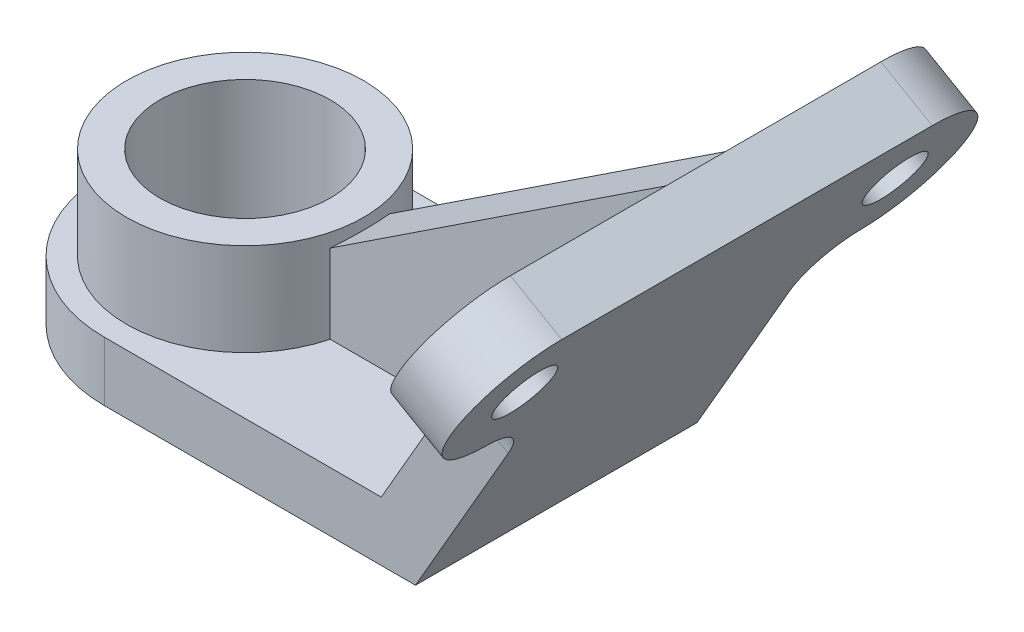
SolidWorks part; units mm, degrees
ref_plane "前视基准面" through (0, 0, 0) normal (0, 0, 1) x (1, 0, 0)
ref_plane "上视基准面" through (0, 0, 0) normal (0, 1, 0) x (1, 0, 0)
ref_plane "右视基准面" through (0, 0, 0) normal (1, 0, 0) x (0, 0, -1)
other "Configuration Table"
sketch "草图1" plane through (0, 0, 0) normal (0, 0, 1) x (1, 0, 0)
  line L1 (0, 0) -> (122, 0)
  line L2 (0, 0) -> (0, 16)
  line L3 (0, 16) -> (112.7624, 16)
  line L5 (122, 0) -> (173.5, 89.2006)
  line L6 (112.7624, 16) -> (159.6436, 97.2006)
  line L7 (173.5, 89.2006) -> (159.6436, 97.2006)
  dimension "D1" = 16
  dimension "D2" = 16
  dimension "D3" = 60
  dimension "D4" = 103
  dimension "D5" = 122
extrude "凸台-拉伸1" add sketch "草图1" along normal mid plane 76
sketch "草图3" plane through (77.6436, -44.8275, 0) normal (-0.866, 0.5, 0) x (0, 0, 1)
  line L0 (-50, 164) -> (50, 164)
  line L1 (0, 0) -> (0, 185.5278) construction
  line L4 (-38, 164) -> (-38, 70.2376)
  line L5 (-38, 70.2376) -> (38, 70.2376)
  line L6 (38, 70.2376) -> (38, 164)
  line L7 (38, 164) -> (-38, 164)
  line L8 (-38, 111.0152) -> (-38, 70.2376)
  line L9 (-38, 70.2376) -> (38, 70.2376)
  line L10 (38, 70.2376) -> (38, 111.0152)
  line L11 (38, 164) -> (-38, 164)
  arc A0 (50.6061, 124.0092) -> (50, 164) centre (50, 144) ccw
  circle A1 centre (50, 144) radius 8
  arc A2 (50.6061, 124.0092) -> (38, 111.0152) centre (51, 111.0152) ccw
  arc A3 (-50.6061, 124.0092) -> (-38, 111.0152) centre (-51, 111.0152) cw
  arc A4 (-50.6061, 124.0092) -> (-50, 164) centre (-50, 144) cw
  circle A5 centre (-50, 144) radius 8
  point P7 (0, 164)
  line M5 (-38, 164) -> (-38, 70.2376)
  line M7 (38, 70.2376) -> (38, 164)
  dimension "D3" = 40
  dimension "D4" = 16
  dimension "D5" = 13
  dimension "D2" = 100
  dimension "D1" = 0
extrude "凸台-拉伸2" add sketch "草图3" against normal up to surface (16 mm away) contours A4 A3 L0 A5 M5 | A2 A0 L0 A1 M7 region at (159.3341, 96.6646, -44) region at (159.3341, 96.6646, 44) up to face at (147.75, 44.6003, 0)
sketch "草图5" plane through (0, 16, 0) normal (0, 1, 0) x (1, 0, 0)
  line L0 (0, 0) -> (94.0384, 0) construction
  line L1 (0, -38) -> (0, 38) construction
  line L2 (112.7624, 38) -> (0, 38) construction
  line L3 (112.7624, -38) -> (0, -38) construction
  line L4 (112.7624, -38) -> (0, -38)
  line L5 (0, -38) -> (0, 38)
  line L6 (112.7624, 38) -> (0, 38)
  line L7 (112.7624, 38) -> (0, 38)
  line L8 (0, 38) -> (0, -38)
  line L9 (0, -38) -> (112.7624, -38)
  line L10 (112.7624, -38) -> (112.7624, 38)
  line L11 (112.7624, 38) -> (38, 38)
  line L13 (38, -38) -> (112.7624, -38)
  line L14 (112.7624, -38) -> (112.7624, 38)
  circle A0 centre (38, 0) radius 38
  circle A1 centre (38, 0) radius 32
  circle A2 centre (38, 0) radius 23
  dimension "D1" = 0
  dimension "D2" = 64
  dimension "D3" = 46
extrude "凸台-拉伸3" add sketch "草图5" along normal blind 25 contours A1 L0 A2 | L0 A1 A2 region at (38, 16, -23.7155) region at (65.5, 16, 0.7155)
extrude "切除-拉伸1" cut sketch "草图5<4>" against normal up to next contours A2
sketch "草图5<4>" plane through (0, 16, 0) normal (0, 1, 0) x (1, 0, 0) same geometry as "草图5"
sketch "草图6" plane through (0, 16, 0) normal (0, 1, 0) x (1, 0, 0)
  line L0 (38, 38) -> (0, 38)
  line L1 (0, 38) -> (0, 0)
  arc A0 (38, 38) -> (0, 0) centre (38, 0) ccw
extrude "切除-拉伸2" cut sketch "草图6" against normal up to next
mirror "镜向1" about plane through (0, 0, 0) normal (0, 0, 1) of "切除-拉伸2"
sketch "草图9" plane through (0, 0, 0) normal (0, 0, 1) x (1, 0, 0)
  line L0 (70, 38) -> (159.6436, 97.2006)
  line L1 (70, 16) -> (70, 41) construction
  line L2 (112.7624, 16) -> (38, 16) construction
  dimension "D1" = 22
rib "筋1" sketch "草图9" sketch "草图9" thickness 16 extrusion direction parallel to sketch draft on no parameters "D1"=16
